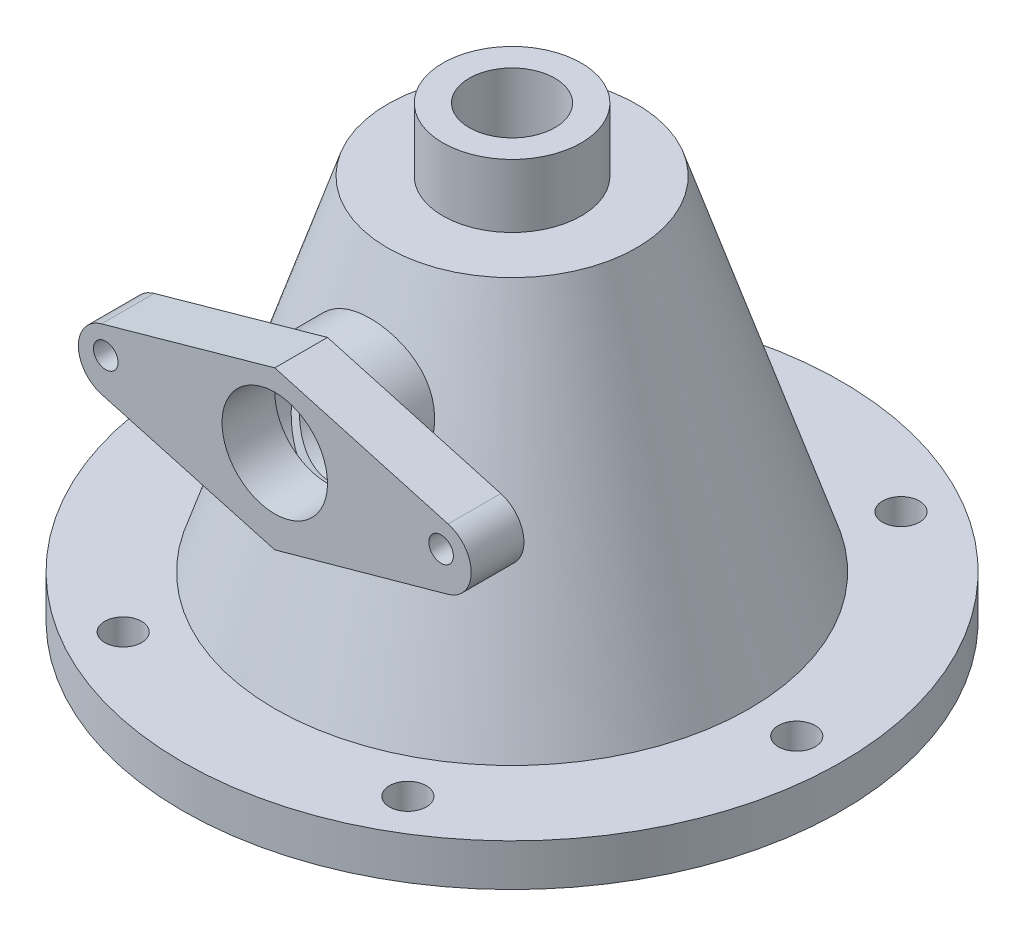
SolidWorks part; units mm, degrees
note: The reader was unsure of these and kept them because the rebuilt part matched: shared geometry of "草图2<2>".
ref_plane "前视基准面" through (0, 0, 0) normal (0, 0, 1) x (1, 0, 0)
ref_plane "上视基准面" through (0, 0, 0) normal (0, 1, 0) x (1, 0, 0)
ref_plane "右视基准面" through (0, 0, 0) normal (1, 0, 0) x (0, 0, -1)
other "Configuration Table"
sketch "草图1" plane through (0, 0, 0) normal (0, 0, 1) x (1, 0, 0)
  line L0 (0, 0) -> (0, -33343.3769) construction
  line L2 (-8.1276, 76.4298) -> (-8.1276, 59.4298)
  line L3 (-8.1276, 59.4298) -> (-20, 59.4298)
  line L4 (-20, 59.4298) -> (-42.368, -8.5702)
  line L5 (-42.368, -8.5702) -> (-62.5, -8.5702)
  line L6 (-62.5, -8.5702) -> (-62.5, -0.5702)
  line L7 (-62.5, -0.5702) -> (-45, -0.5702)
  line L8 (-45, -0.5702) -> (-25.0272, 60.1482)
  line L9 (-25.0272, 60.1482) -> (-23.6189, 64.4298)
  line L10 (-23.6189, 64.4298) -> (-13.1276, 64.4298)
  line L13 (-13.1276, 64.4298) -> (-13.1276, 76.4298)
  line L14 (-13.1276, 76.4298) -> (-8.1276, 76.4298)
  dimension "D1" = 125
  dimension "D2" = 90
  dimension "D3" = 8
  dimension "D4" = 5
  dimension "D5" = 40
  dimension "D6" = 85
  dimension "D7" = 12
  dimension "D8" = 5
  dimension "D9" = 5
revolve "旋转1" add sketch "草图1" angle 360 about L0
sketch "草图2" plane through (0, 0, 0) normal (0, 0, 1) x (1, 0, 0)
  line L0 (-62.5, -8.5702) -> (62.5, -8.5702) construction
  circle A0 centre (0, 41.4298) radius 10
  dimension "D2" = 20
  dimension "D1" = 50
extrude "凸台-拉伸2" add sketch "草图2" along normal blind 45
sketch "草图4" plane through (0, 0, 45) normal (0, 0, 1) x (1, 0, 0)
  line L0 (0, 41.4298) -> (0, 55.4197)
  line L1 (0, 55.4197) -> (-32.869, 46.2129)
  line L2 (-32.8557, 34.654) -> (0, 25.5321)
  line L3 (0, 25.5321) -> (0, 41.4298)
  line L4 (32.8557, 34.654) -> (0, 25.5321)
  line L5 (0, 55.4197) -> (32.869, 46.2129)
  arc A0 (-32.869, 46.2129) -> (-32.8557, 34.654) centre (-31.2507, 40.4353) ccw
  arc A1 (32.869, 46.2129) -> (32.8557, 34.654) centre (31.2507, 40.4353) cw
  circle M6 centre (0, 41.4298) radius 10
  dimension "D1" = 6
extrude "凸台-拉伸4" add sketch "草图4" against normal blind 10 contours L1 A0 L2 L3 L0 M6 | A1 L5 L0 L3 L4 M6
extrude "切除-拉伸1" cut sketch "草图2<2>" along normal through all
sketch "草图2<2>" plane through (0, 0, 0) normal (0, 0, 1) x (1, 0, 0) same geometry as "草图2"
sketch "草图5" plane through (0, 0, 45) normal (0, 0, 1) x (1, 0, 0)
  circle A0 centre (0, 41.4298) radius 12
  circle A1 centre (0, 41.4298) radius 13.0583
  dimension "D1" = 24
extrude "凸台-拉伸5" add sketch "草图5" against normal up to next
sketch "草图8" plane through (0, 0, 45) normal (0, 0, 1) x (1, 0, 0)
  circle A0 centre (-32.0549, 41.4298) radius 2.3323
  circle A1 centre (31.5323, 41.4298) radius 2.3323
extrude "切除-拉伸2" cut sketch "草图8" against normal up to next and the other way through all contours A0 | A1
sketch "草图9" plane through (0, 0, 0) normal (0, 1, 0) x (1, 0, 0)
  line L0 (0, 0) -> (0, 50000) construction
  line L1 (0, 0) -> (50000, 0) construction
  circle A0 centre (-53.9887, 0) radius 3.5
  circle A1 centre (-26.9944, 46.7556) radius 3.5
  circle A2 centre (26.9944, 46.7556) radius 3.5
  circle A3 centre (53.9887, 0) radius 3.5
  circle A4 centre (26.9944, -46.7556) radius 3.5
  circle A5 centre (-26.9944, -46.7556) radius 3.5
  point P19 (0, 0)
  dimension "D1" = 7
  dimension "D2" = 6
extrude "切除-拉伸3" cut sketch "草图9" against normal up to next contours A0 | A1 | A3 | A2 | A4 | A5
